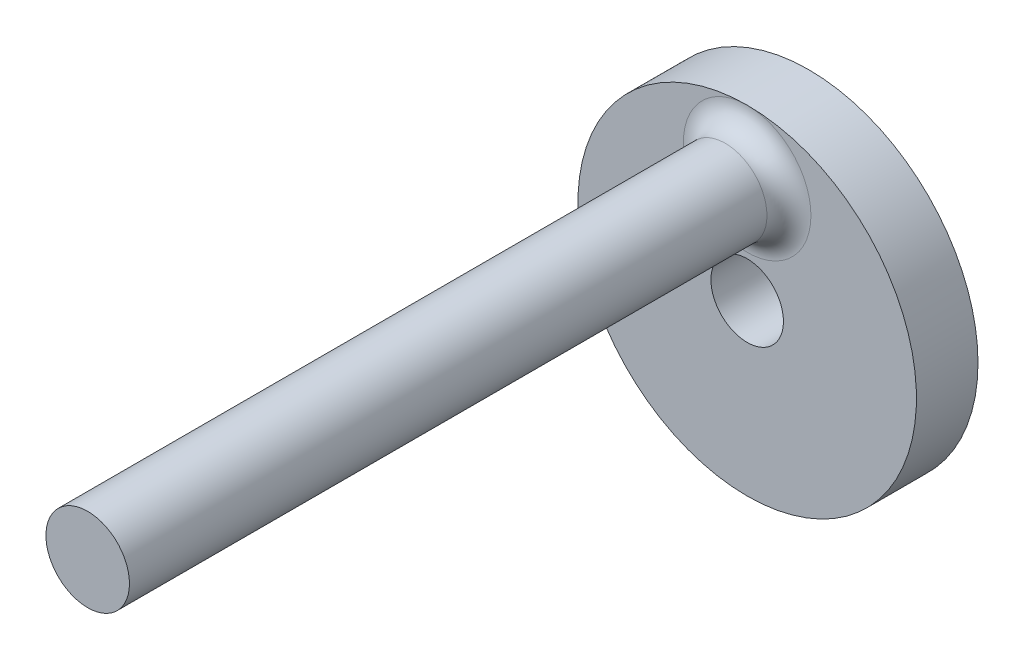
SolidWorks part; units mm, degrees
ref_plane "Plan de face" through (0, 0, 0) normal (0, 0, 1) x (1, 0, 0)
ref_plane "Plan de dessus" through (0, 0, 0) normal (0, 1, 0) x (1, 0, 0)
ref_plane "Plan de droite" through (0, 0, 0) normal (1, 0, 0) x (0, 0, -1)
sketch "Esquisse1" plane through (0, 0, 0) normal (0, 0, 1) x (1, 0, 0)
  circle A0 centre (0, 0) radius 7.7
  dimension "D1" = 15.4
extrude "Boss.-Extru.1" add sketch "Esquisse1" along normal blind 2.8
sketch "Esquisse2" plane through (0, 0, 2.8) normal (0, 0, 1) x (1, 0, 0)
  circle A0 centre (0, 4.8) radius 1.9
  dimension "D2" = 3.8
  dimension "D1" = 4.8
extrude "Boss.-Extru.2" add sketch "Esquisse2" along normal blind 30
sketch "Esquisse3" plane through (0, 0, 2.8) normal (0, 0, 1) x (1, 0, 0)
  circle A0 centre (0, 0) radius 1.65
  dimension "D1" = 3.3
extrude "Enlèv. mat.-Extru.1" cut sketch "Esquisse3" against normal through all
fillet "Congé2" radius 1 1 edges at (1.9, 4.8, 2.8)
